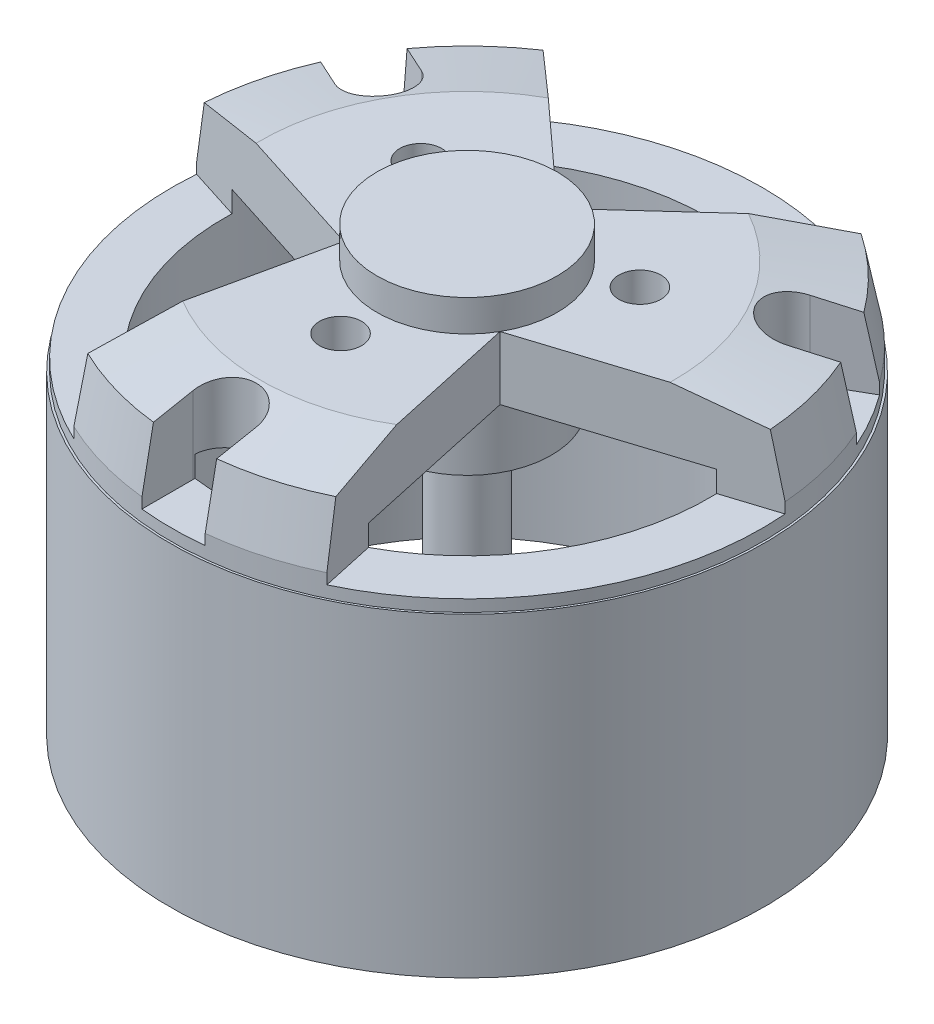
SolidWorks part; units mm, degrees
material "Acciaio al carbonio semplice"
ref_plane "Piano frontale" through (0, 0, 0) normal (0, 0, 1) x (1, 0, 0)
ref_plane "Piano superiore" through (0, 0, 0) normal (0, 1, 0) x (1, 0, 0)
ref_plane "Piano destro" through (0, 0, 0) normal (1, 0, 0) x (0, 0, -1)
sketch "Schizzo1" plane through (0, 0, 0) normal (0, 1, 0) x (1, 0, 0)
  circle A0 centre (0, 0) radius 14
  dimension "D1" = 28
extrude "Estrusione-Estrusione1" add sketch "Schizzo1" along normal blind 19.5
sketch "Schizzo2" plane through (0, 19.5, 0) normal (0, 1, 0) x (1, 0, 0)
  line L0 (0, 0) -> (16.0676, 9.2766) construction
  line L1 (0, 0) -> (-5.1962, 3) construction
  line L2 (0, 0) -> (0, -16.2401) construction
  line L3 (0.1113, 4.1735) -> (-7.9545, 11.5207)
  line L4 (-13.9545, 1.1284) -> (-3.5587, -2.1831)
  line L5 (7.9545, 11.5207) -> (-0.1113, 4.1735)
  line L6 (3.5587, -2.1831) -> (13.9545, 1.1284)
  line L7 (6, -12.6491) -> (3.67, -1.9904)
  line L8 (-3.67, -1.9904) -> (-6, -12.6491)
  circle A0 centre (-5.1962, 3) radius 1
  circle A1 centre (5.1962, 3) radius 1
  circle A2 centre (0, -6) radius 1
  arc A3 (-7.9545, 11.5207) -> (-13.9545, 1.1284) centre (0, 0) ccw
  circle A4 centre (0, 0) radius 14 construction
  arc A6 (13.9545, 1.1284) -> (7.9545, 11.5207) centre (0, 0) ccw
  arc A7 (-6, -12.6491) -> (6, -12.6491) centre (0, 0) ccw
  point P13 (0, 0)
  point P27 (0, 0)
  circle M4 centre (0, 0) radius 14
  dimension "D3" = 3
  dimension "D1" = 3.67
  dimension "D2" = 120
  dimension "D5" = 12
  dimension "D6" = 3.67
  dimension "D4" = 3
extrude "Taglio-Estrusione1" cut sketch "Schizzo2" against normal blind 4 contours L5 L3 M4 | L7 L6 M4 | L8 L4 M4 | A2 | A0 | A1
sketch "Schizzo3" plane through (0, 19.5, 0) normal (0, 1, 0) x (1, 0, 0)
  circle A0 centre (0, 0) radius 4.2749
extrude "Estrusione-Estrusione2" add sketch "Schizzo3" along normal blind 1.5
sketch "Schizzo4" plane through (0, 0, 0) normal (0, -1, 0) x (1, 0, 0)
  circle A0 centre (0, 0) radius 11.5
  circle A1 centre (0, 0) radius 14 construction
  dimension "D1" = 2.5
extrude "Taglio-Estrusione2" cut sketch "Schizzo4" against normal blind 16.5
sketch "Schizzo5" plane through (0, 21, 0) normal (0, 1, 0) x (1, 0, 0)
  circle A0 centre (0, 0) radius 1.5
extrude "Taglio-Estrusione3" cut sketch "Schizzo5" against normal blind 16.5
sketch "Schizzo6" plane through (0, 19.5, 0) normal (0, 1, 0) x (1, 0, 0)
  line L0 (1.5, -11.5) -> (1.5, -13.9194)
  line L1 (-1.5, -11.5) -> (-1.5, -13.9194)
  line L2 (-9.2093, 7.049) -> (-11.3046, 8.2587)
  line L3 (-10.7093, 4.451) -> (-12.8046, 5.6607)
  line L4 (10.7093, 4.451) -> (12.8046, 5.6607)
  line L5 (9.2093, 7.049) -> (11.3046, 8.2587)
  arc A0 (1.5, -11.5) -> (-1.5, -11.5) centre (0, -11.5) ccw
  arc A1 (-6, -12.6491) -> (6, -12.6491) centre (0, 0) ccw construction
  arc A2 (1.5, -13.9194) -> (-1.5305, -13.9161) centre (0, 0) cw
  arc A3 (-10.7093, 4.451) -> (-9.2093, 7.049) centre (-9.9593, 5.75) ccw
  arc A4 (-12.8046, 5.6607) -> (-11.2864, 8.2835) centre (0, 0) cw
  arc A5 (9.2093, 7.049) -> (10.7093, 4.451) centre (9.9593, 5.75) ccw
  arc A6 (11.3046, 8.2587) -> (12.8169, 5.6326) centre (0, 0) cw
  point P2 (0, -14)
  point P27 (0, 0)
  arc M3 (-6, -12.6491) -> (6, -12.6491) centre (0, 0) ccw
  dimension "D1" = 2.5
  dimension "D2" = 3
extrude "Taglio-Estrusione4" cut sketch "Schizzo6" against normal blind 4 contours L0 A0 L1 M3 | A6 L5 A5 L4 | A4 L3 A3 L2
sketch "Schizzo7" plane through (0, 21, 0) normal (0, 1, 0) x (1, 0, 0)
  circle A0 centre (0, 0) radius 1.5
extrude "Estrusione-Estrusione3" add sketch "Schizzo7" against normal blind 27.5
sketch "Schizzo8" plane through (0, 16.5, 0) normal (0, -1, 0) x (1, 0, 0)
  circle A0 centre (0, 0) radius 4
extrude "Estrusione-Estrusione4" add sketch "Schizzo8" along normal blind 3
sketch "Schizzo9" plane through (0, 0, 0) normal (0, 0, 1) x (1, 0, 0)
  line L0 (-14, 15.5) -> (-14, 0) construction
  line L1 (-14, 14.9388) -> (-14.1, 14.9388)
  line L2 (-14, 14.9388) -> (-14, 0)
  line L3 (-14, 0) -> (-14.1, 0)
  line L4 (-14.1, 14.9388) -> (-14.1, 0)
  dimension "D1" = 0.1
revolve "Rivoluzione1" add sketch "Schizzo9" angle 360 about axis through (0, -6.5, 0) along (0, 1, 0)
chamfer "Smusso1" distance 3.5 angle 11 6 edges at (9.7667, 19.5, -10.0306) (13.5701, 19.5, -3.4429) (3.8034, 19.5, 13.4735) (-3.8034, 19.5, 13.4735) (-13.5701, 19.5, -3.4429) (-9.7667, 19.5, -10.0306)
chamfer "Smusso2" distance 3.5 angle 11 3 edges at (-12.9386, 19.5, -3.1634) (3.7297, 19.5, 12.7868) (12.9386, 19.5, -3.1634)
